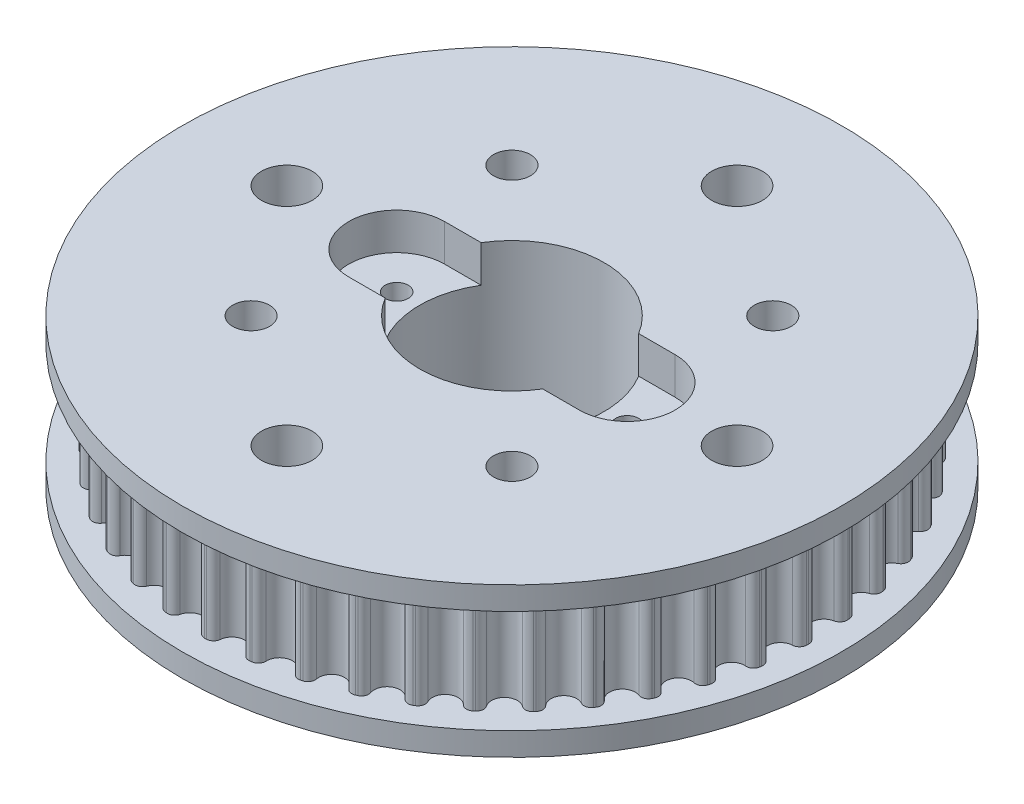
SolidWorks part; units mm, degrees
ref_plane "Front Plane" through (0, 0, 0) normal (0, 0, 1) x (1, 0, 0)
ref_plane "Top Plane" through (0, 0, 0) normal (0, 1, 0) x (1, 0, 0)
ref_plane "Right Plane" through (0, 0, 0) normal (1, 0, 0) x (0, 0, -1)
sketch "Sketch1" plane through (0, 0, 0) normal (0, 1, 0) x (1, 0, 0)
  line L0 (0, 0) -> (0, 21.1048) construction
  line L1 (0, 0) -> (2.8913, 20.5726) construction
  circle A0 centre (0, 0) radius 21.1048 construction
  circle A1 centre (0, 0) radius 19.8848 construction
  circle A2 centre (0, 20.7748) radius 0.89 construction
  circle A5 centre (2.8913, 20.5726) radius 0.89 construction
  arc A6 (0, 19.8848) -> (0.8792, 20.6366) centre (0, 20.7748) ccw
  arc A7 (0.8792, 20.6366) -> (1.4065, 21.0579) centre (1.3731, 20.559) cw
  arc A8 (1.5379, 21.0487) -> (2.0014, 20.5582) centre (1.5015, 20.55) cw
  arc A9 (2.7674, 19.6913) -> (2.0014, 20.5582) centre (2.8913, 20.5726) cw
  arc A10 (1.4065, 21.0579) -> (1.5379, 21.0487) centre (0, 0) cw
  arc A11 (0, 19.8848) -> (2.7674, 19.6913) centre (0, 0) ccw
  dimension "D1" = 42.2096
  dimension "D3" = 1.78
  dimension "D4" = 0.5
  dimension "D2" = 1.22
  dimension "D5" = 8
extrude "Boss-Extrude1" add sketch "Sketch1" along normal mid plane 7.112
ref_axis "Axis1" through (0, 3.3, 0) along (0, -1, 0)
pattern_circular "CirPattern1" count 45 over 360 about axis through (0, 3.3, 0) along (0, -1, 0) of "Boss-Extrude1"
sketch "Sketch2" plane through (0, 0, 0) normal (1, 0, 0) x (0, 0, -1)
  line L0 (-20.6477, 3.556) -> (-21.1047, 3.556) construction
  line L4 (22.6922, 5.1435) -> (6.35, 5.1435)
  line L5 (22.6922, 5.1435) -> (22.6922, 3.556)
  line L6 (-22.6922, 3.556) -> (22.6922, 3.556) construction
  line L7 (-22.6922, 3.556) -> (-22.6922, 5.1435) construction
  line L8 (-22.6922, 5.1435) -> (22.6922, 5.1435) construction
  line L9 (22.6922, 3.556) -> (22.6922, 5.1435) construction
  line L10 (-22.6922, 3.556) -> (22.6922, 5.1435) construction
  line L11 (-22.6922, 5.1435) -> (22.6922, 3.556) construction
  line L12 (-21.1047, 3.556) -> (-21.1047, -3.556) construction
  line L13 (0, 3.3) -> (0, -3.3) construction
  line L14 (6.35, 5.1435) -> (6.35, 3.556)
  line L16 (22.6922, 3.556) -> (6.35, 3.556)
  line L17 (6.35, 5.1435) -> (6.35, 3.556)
  point P0 (0, 4.3498)
  dimension "D1" = 1.5875
  dimension "D2" = 1.5875
  dimension "D3" = 6.35
revolve "Revolve3" add sketch "Sketch2" angle 360 about axis through (0, 3.3, 0) along (0, -1, 0) region at (0, 4.3498, -14.5211)
mirror "Mirror1" about plane through (0, 0, 0) normal (0, 1, 0) of "Revolve3"
sketch "Sketch3" plane through (0, 3.556, 0) normal (0, 1, 0) x (1, 0, 0)
  line L1 (-8.9803, -8.9803) -> (8.9803, -8.9803) construction
  line L2 (-8.9803, -8.9803) -> (-8.9803, 8.9803) construction
  line L3 (-8.9803, 8.9803) -> (8.9803, 8.9803) construction
  line L4 (8.9803, -8.9803) -> (8.9803, 8.9803) construction
  line L5 (-8.9803, -8.9803) -> (8.9803, 8.9803) construction
  line L6 (-8.9803, 8.9803) -> (8.9803, -8.9803) construction
  circle A0 centre (-15.5, 0) radius 1.7462
  circle A1 centre (0, 0) radius 6.35
  circle A2 centre (0, 0) radius 6.35
  circle A3 centre (0, 15.5) radius 1.7462
  circle A4 centre (15.5, 0) radius 1.7462
  circle A5 centre (0, -15.5) radius 1.7462
  circle A6 centre (-8.9803, 8.9803) radius 1.27
  circle A7 centre (8.9803, 8.9803) radius 1.27
  circle A8 centre (8.9803, -8.9803) radius 1.27
  circle A9 centre (-8.9803, -8.9803) radius 1.27
  point P14 (0, 0)
  dimension "D3" = 3.4925
  dimension "D5" = 2.54
  dimension "D2" = 15.5
  dimension "D6" = 25.4
  dimension "D1" = 0
  dimension "D4" = 4
extrude "Cut-Extrude1" cut sketch "Sketch3" against normal through all both and the other way through all
sketch "Sketch4" plane through (0, 5.1435, 0) normal (0, 1, 0) x (1, 0, 0)
  line L0 (-7.9375, 0) -> (7.9375, 0) construction
  line L1 (-7.9375, 3.302) -> (7.9375, 3.302)
  line L2 (-7.9375, -3.302) -> (7.9375, -3.302)
  arc A0 (-7.9375, 3.302) -> (-7.9375, -3.302) centre (-7.9375, 0) ccw
  arc A1 (7.9375, -3.302) -> (7.9375, 3.302) centre (7.9375, 0) ccw
  point P3 (0, 0)
  dimension "D1" = 15.875
  dimension "D2" = 6.604
extrude "Cut-Extrude2" cut sketch "Sketch4" against normal blind 2.54
sketch "Sketch5" plane through (0, 2.6035, 0) normal (0, 1, 0) x (1, 0, 0)
  circle A0 centre (-7.9375, 0) radius 0.7938
  circle A1 centre (7.9375, 0) radius 0.7937
  dimension "D1" = 1.5875
extrude "Cut-Extrude3" cut sketch "Sketch5" against normal through all
equation "\"TEETH_NUM\"= 45"
equation "\"TOOTH_PITCH\"= 3mm"
equation "\"PITCH_LINE_OFFSET\"= .015in"
equation "\"DIAMETER_PER_GROOVE\"= .954925mm"
equation "\"PITCH_DIAMETER\"= \"TEETH_NUM\" * \"DIAMETER_PER_GROOVE\""
equation "\"OUTSIDE_DIAMETER\"= \"PITCH_DIAMETER\" - \"PITCH_LINE_OFFSET\" * 2"
equation "\"D1@Sketch1\"=\"OUTSIDE_DIAMETER\""
equation "\"TOOTH_HEIGHT\"= 1.22mm"
equation "\"D2@Sketch1\"=\"TOOTH_HEIGHT\""
equation "\"TOOTH_DIAMETER\"= 1.78mm"
equation "\"INTERNAL_RADIUS\"= .5mm"
equation "\"D3@Sketch1\"=\"TOOTH_DIAMETER\""
equation "\"D5@Sketch1\"=360 / \"TEETH_NUM\""
equation "\"D4@Sketch1\"=\"INTERNAL_RADIUS\""
equation "\"D1@CirPattern1\"=\"TEETH_NUM\""
equation "\"BELT_GAP\"= 7mm"
